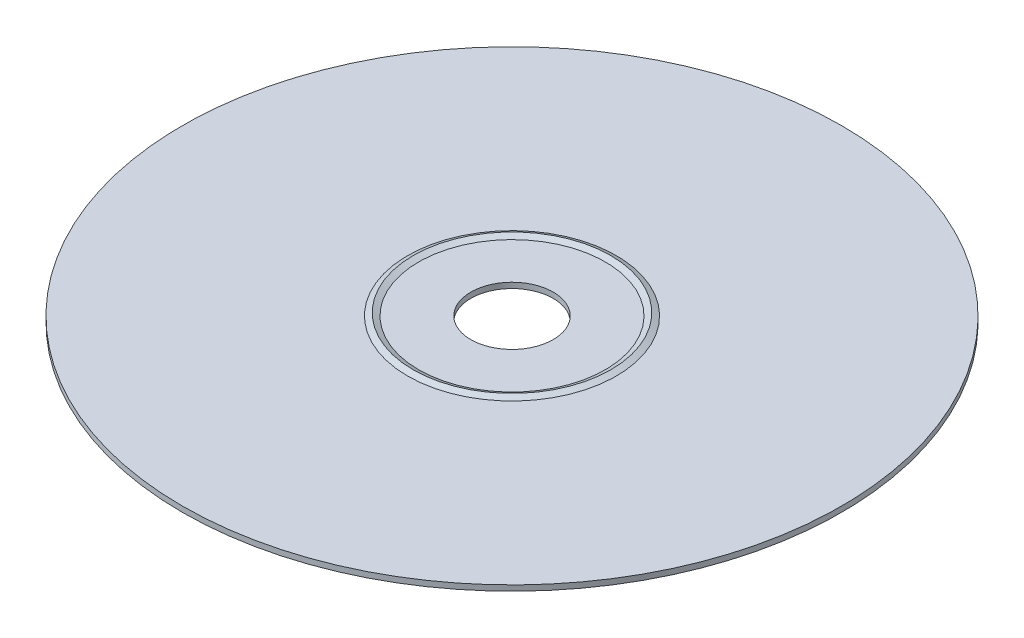
SolidWorks part; units mm, degrees
material "ABS PC"
ref_plane "Front Plane" through (0, 0, 0) normal (0, 0, 1) x (1, 0, 0)
ref_plane "Top Plane" through (0, 0, 0) normal (0, 1, 0) x (1, 0, 0)
ref_plane "Right Plane" through (0, 0, 0) normal (1, 0, 0) x (0, 0, -1)
sketch "Sketch1" plane through (0, 0, 0) normal (0, 1, 0) x (1, 0, 0)
  circle A0 centre (0, 0) radius 60
  circle A1 centre (0, 0) radius 7.5
  dimension "D1" = 120
  dimension "D2" = 15
extrude "Boss-Extrude1" add sketch "Sketch1" along normal blind 1
sketch "Sketch2" plane through (0, 1, 0) normal (0, 1, 0) x (1, 0, 0)
  circle A0 centre (0, 0) radius 17
  circle A1 centre (0, 0) radius 19
  dimension "D1" = 34
  dimension "D2" = 2
extrude "Boss-Extrude2" add sketch "Sketch2" along normal blind 0.5
chamfer "Chamfer1" distance 1 distance2 0.5 2 edges at (0, 1.5, 19) (0, 1.5, 17) first distance on face at (0, 1.5, 19)
sketch "Sketch3" plane through (0, 0, 0) normal (0, -1, 0) x (1, 0, 0)
  circle A0 centre (0, 0) radius 19.5806
  circle A1 centre (0, 0) radius 59
  circle A2 centre (0, 0) radius 60 construction
  dimension "D1" = 1
extrude "Boss-Extrude3" add sketch "Sketch3" along normal blind 0.001
sketch "Sketch4" plane through (0, -0.001, 0) normal (0, -1, 0) x (1, 0, 0)
  line L2 (-32.7319, -30.9335) -> (34.6716, -30.9335)
  line L3 (-25.9431, -40.8743) -> (27.6403, -40.8743)
  line L4 (-32.7319, -30.6335) -> (34.6716, -30.6335)
  line L5 (-25.9431, -40.5743) -> (27.6403, -40.5743)
  arc A0 (-25.9431, -40.5743) -> (-25.9431, -40.8743) centre (-25.9431, -40.7243) ccw
  arc A1 (-32.7319, -30.6335) -> (-32.7319, -30.9335) centre (-32.7319, -30.7835) ccw
  arc A2 (34.6716, -30.6335) -> (34.6716, -30.9335) centre (34.6716, -30.7835) cw
  arc A3 (27.6403, -40.5743) -> (27.6403, -40.8743) centre (27.6403, -40.7243) cw
  dimension "D1" = 0.3
  dimension "D2" = 0.3
extrude "Cut-Extrude1" cut sketch "Sketch4" against normal blind 0.001
sketch "Sketch5" plane through (0, -0.001, 0) normal (0, -1, 0) x (1, 0, 0)
  text T0 "<b>DVD</b>" font "Cooper Black" height 5
  text T1 "<b>4.7 GB</b>"
  text T2 "<b>1-16x </b>"
extrude "Cut-Extrude2" cut sketch "Sketch5" against normal blind 0.001
sketch "Sketch6" plane through (0, -0.001, 0) normal (0, -1, 0) x (1, 0, 0)
  text T0 "JVC  DVD - R" font "Cooper Black" height 3.5
extrude "Cut-Extrude3" cut sketch "Sketch6" against normal blind 0.001
